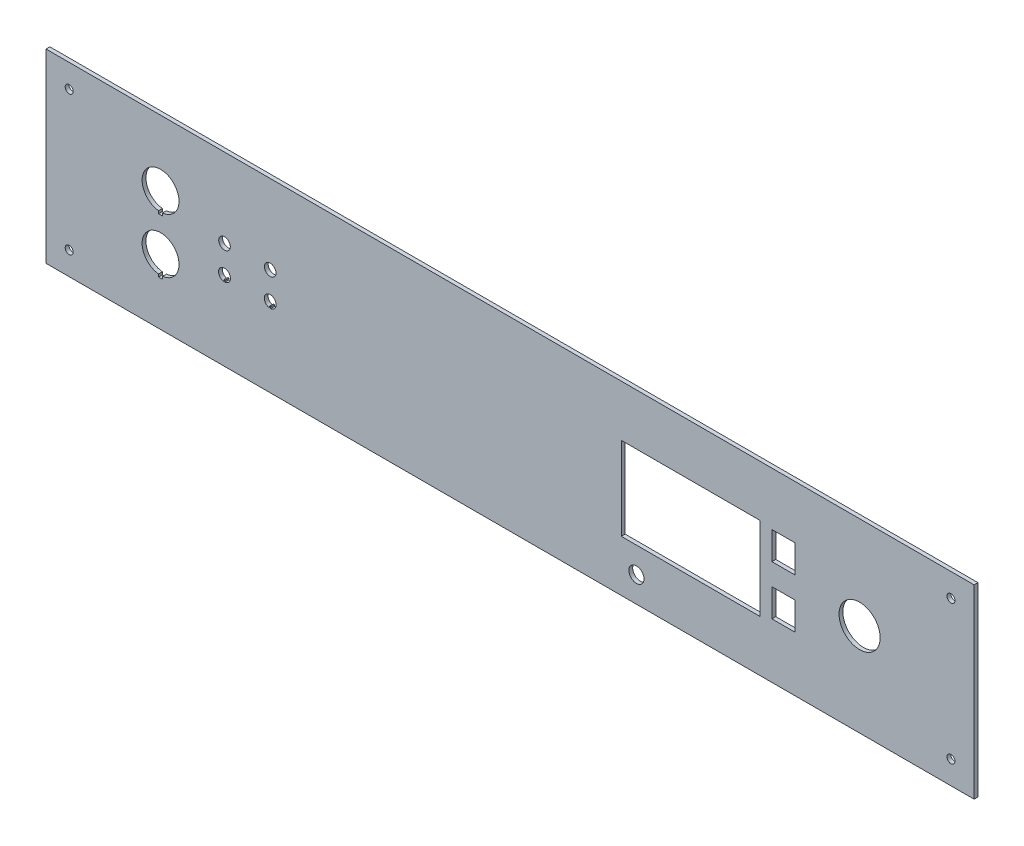
SolidWorks part; units mm, degrees
ref_plane "Front Plane" through (0, 0, 0) normal (0, 0, 1) x (1, 0, 0)
ref_plane "Top Plane" through (0, 0, 0) normal (0, 1, 0) x (1, 0, 0)
ref_plane "Right Plane" through (0, 0, 0) normal (1, 0, 0) x (0, 0, -1)
sketch "Sketch1" plane through (0, 0, 0) normal (0, 0, 1) x (1, 0, 0)
  line L1 (-254, 50.8) -> (254, 50.8)
  line L2 (-254, 50.8) -> (-254, -50.8)
  line L3 (-254, -50.8) -> (254, -50.8)
  line L4 (254, 50.8) -> (254, -50.8)
  line L5 (-254, 50.8) -> (254, -50.8) construction
  line L6 (-254, -50.8) -> (254, 50.8) construction
  point P0 (0, 0)
  dimension "D1" = 508
  dimension "D2" = 101.6
extrude "Front panel" add sketch "Sketch1" along normal blind 2.1
sketch "Sketch7" plane through (0, 0, 2.1) normal (0, 0, 1) x (1, 0, 0)
  line L0 (-241.3, 38.1) -> (241.3, -38.1) construction
  circle A0 centre (-241.3, 38.1) radius 2.2
  circle A1 centre (-241.3, -38.1) radius 2.2
  circle A2 centre (241.3, -38.1) radius 2.2
  circle A3 centre (241.3, 38.1) radius 2.2
  dimension "D1" = 4.4
  dimension "D2" = 482.6
  dimension "D3" = 76.2
extrude "Mounting holes" cut sketch "Sketch7" against normal up to next
sketch "Sketch2" plane through (0, 0, 2.1) normal (0, 0, 1) x (1, 0, 0)
  line L0 (-191.3, 15) -> (-191.3, -15) construction
  line L1 (-192.4, 4.9601) -> (-192.4, 3.5)
  line L2 (-192.4, 3.5) -> (-190.2, 3.5)
  line L3 (-190.2, 3.5) -> (-190.2, 4.9601)
  line L4 (-192.4, -25.0399) -> (-192.4, -26.5)
  line L5 (-192.4, -26.5) -> (-190.2, -26.5)
  line L6 (-190.2, -26.5) -> (-190.2, -25.0399)
  arc A0 (-190.2, 4.9601) -> (-192.4, 4.9601) centre (-191.3, 15) ccw
  arc A1 (-190.2, -25.0399) -> (-192.4, -25.0399) centre (-191.3, -15) ccw
  circle A2 centre (-241.3, 38.1) radius 2.2 construction
  point P4 (-191.3, 0)
  point P12 (-191.3, 3.5)
  dimension "D1" = 20.2
  dimension "D2" = 30
  dimension "D3" = 50
  dimension "D4" = 2.2
  dimension "D5" = 11.5
  dimension "D6" = 11.5
extrude "Start/stop" cut sketch "Sketch2" against normal through all
sketch "Sketch3" plane through (0, 0, 2.1) normal (0, 0, 1) x (1, 0, 0)
  line L0 (-191.3, 15) -> (-191.3, -15) construction
  line L1 (-156.6, -10.7361) -> (-156.6, -9.85)
  line L2 (-156.6, -9.85) -> (-156, -9.85)
  line L3 (-156, -9.85) -> (-156, -10.7361)
  line L4 (-131.6, -10.7361) -> (-131.6, -9.85)
  line L5 (-131.6, -9.85) -> (-131, -9.85)
  line L6 (-131, -9.85) -> (-131, -10.7361)
  line L7 (-156.3, 7.5) -> (-156.3, -7.5) construction
  arc A0 (-156, -10.7361) -> (-156.6, -10.7361) centre (-156.3, -7.5) ccw
  circle A1 centre (-156.3, 7.5) radius 3.175
  circle A2 centre (-131.3, 7.5) radius 3.175
  circle A3 centre (-191.3, 15) radius 10.1 construction
  circle A4 centre (-191.3, -15) radius 10.1 construction
  circle A5 centre (-191.3, 15) radius 10.1 construction
  circle A6 centre (-191.3, -15) radius 10.1 construction
  arc A7 (-131, -10.7361) -> (-131.6, -10.7361) centre (-131.3, -7.5) ccw
  point P9 (-156.3, 0)
  point P14 (-191.3, 0)
  point P17 (-156.3, -9.85)
  point P22 (-131.3, -9.85)
  dimension "D1" = 6.35
  dimension "D2" = 6.5
  dimension "D3" = 5.6
  dimension "D4" = 15
  dimension "D5" = 0.6
  dimension "D6" = 25
  dimension "D7" = 35
extrude "Mode select" cut sketch "Sketch3" against normal through all
sketch "Sketch4" plane through (0, 0, 2.1) normal (0, 0, 1) x (1, 0, 0)
  line L0 (-191.3, 15) -> (-191.3, -15) construction
  line L1 (60.8601, 22.75) -> (136.8601, 22.75)
  line L2 (60.8601, 22.75) -> (60.8601, -22.75)
  line L3 (60.8601, -22.75) -> (136.8601, -22.75)
  line L4 (136.8601, 22.75) -> (136.8601, -22.75)
  line L5 (60.8601, 22.75) -> (136.8601, -22.75) construction
  line L6 (60.8601, -22.75) -> (136.8601, 22.75) construction
  circle A4 centre (-191.3, -15) radius 10.1 construction
  circle A5 centre (-191.3, -15) radius 10.1 construction
  point P0 (98.8601, 0)
  point P10 (-191.3, 0)
  dimension "D1" = 45.5
  dimension "D2" = 76
extrude "LCD cutout" cut sketch "Sketch4" against normal through all
sketch "Sketch5" plane through (0, 0, 2.1) normal (0, 0, 1) x (1, 0, 0)
  circle A0 centre (191.3, 0) radius 11.25
  circle A1 centre (241.3, 38.1) radius 2.2 construction
  point P4 (-166.8287, 0)
  dimension "D1" = 22.5
  dimension "D2" = 50
extrude "E-stop cutout" cut sketch "Sketch5" against normal through all
sketch "Sketch6" plane through (0, 0, 2.1) normal (0, 0, 1) x (1, 0, 0)
  line L0 (141.8601, -22.75) -> (159.8496, -22.75) construction
  line L1 (143.3201, 21.7025) -> (156.0201, 21.7025)
  line L2 (143.3201, 21.7025) -> (143.3201, 6.4625)
  line L3 (143.3201, 6.4625) -> (156.0201, 6.4625)
  line L4 (156.0201, 21.7025) -> (156.0201, 6.4625)
  line L5 (143.3201, 21.7025) -> (156.0201, 6.4625) construction
  line L6 (143.3201, 6.4625) -> (156.0201, 21.7025) construction
  line L7 (143.3201, -5.415) -> (156.0201, -5.415)
  line L8 (143.3201, -5.415) -> (143.3201, -20.655)
  line L9 (143.3201, -20.655) -> (156.0201, -20.655)
  line L10 (156.0201, -5.415) -> (156.0201, -20.655)
  line L11 (143.3201, -5.415) -> (156.0201, -20.655) construction
  line L12 (143.3201, -20.655) -> (156.0201, -5.415) construction
  line L13 (60.8601, -22.75) -> (136.8601, -22.75) construction
  line L14 (141.8601, 22.75) -> (158.6931, 22.75) construction
  line L15 (136.8601, 22.75) -> (60.8601, 22.75) construction
  line L16 (141.8601, 22.75) -> (141.8601, 20.3374) construction
  line L17 (141.8601, -22.75) -> (141.8601, 12.4166) construction
  line L18 (136.8601, -22.75) -> (136.8601, 22.75) construction
  point P0 (149.6701, 14.0825)
  point P5 (149.6701, -13.035)
  dimension "D1" = 15.24
  dimension "D2" = 12.7
  dimension "D3" = 2.095
  dimension "D4" = 2.095
  dimension "D5" = 1.46
  dimension "D6" = 1.46
  dimension "D7" = 5
extrude "LCD pushbuttons" cut sketch "Sketch6" against normal through all
sketch "Sketch8" plane through (0, 0, 2.1) normal (0, 0, 1) x (1, 0, 0)
  line L0 (69.1601, -22.75) -> (69.1601, -50.8) construction
  line L1 (60.8601, -22.75) -> (136.8601, -22.75) construction
  line L2 (-254, -50.8) -> (254, -50.8) construction
  line L3 (60.8601, 22.75) -> (60.8601, -22.75) construction
  circle A0 centre (69.1601, -36.775) radius 4.15
  dimension "D1" = 8.3
  dimension "D2" = 8.3
extrude "ERROR indicator" cut sketch "Sketch8" against normal up to next
